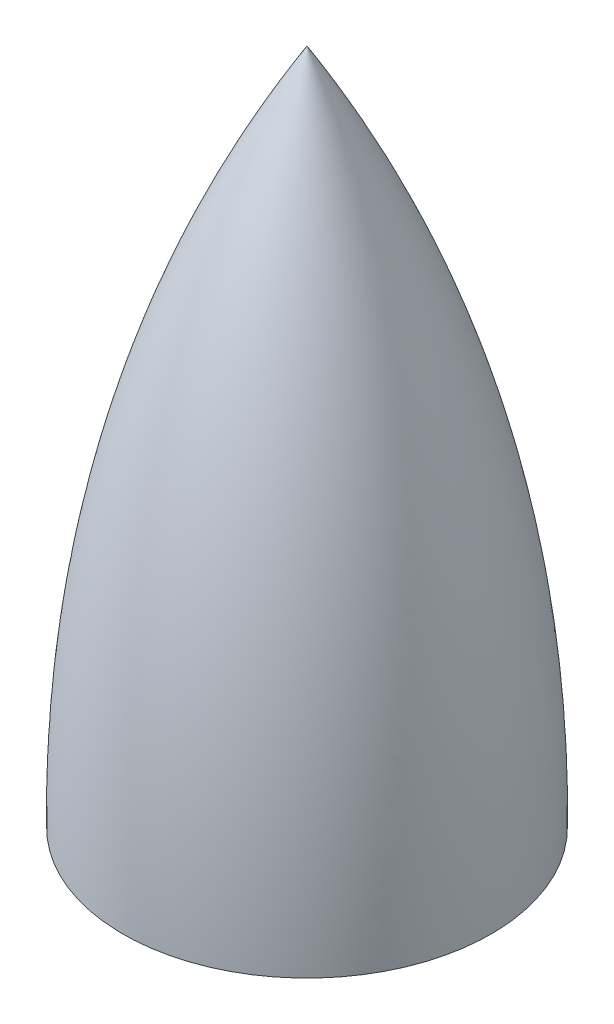
SolidWorks part; units mm, degrees
ref_plane "Front Plane" through (0, 0, 0) normal (0, 0, 1) x (1, 0, 0)
ref_plane "Top Plane" through (0, 0, 0) normal (0, 1, 0) x (1, 0, 0)
ref_plane "Right Plane" through (0, 0, 0) normal (1, 0, 0) x (0, 0, -1)
sketch "Sketch1" plane through (0, 0, 0) normal (0, 1, 0) x (1, 0, 0)
  circle A0 centre (0, 0) radius 101.6
sketch "Sketch2" plane through (0, 0, 0) normal (0, 0, 1) x (1, 0, 0)
  line L0 (0, 0) -> (0, 393.6864)
  line L1 (101.6, 0) -> (-101.6, 0) construction
  line L3 (0, 393.6864) -> (0, 377.4357)
  line L4 (-101.6, 0) -> (-107.95, 0)
  line L5 (-68.4237, 241.4942) -> (-71.5987, 241.4942)
  line L6 (0, 393.6864) -> (0, 396.8614)
  spline S0 degree 2 poles (-101.6, 0) (-107.046, 212.9876) (0, 393.6864) knots 0 0 0 1 1 1
  spline S1 degree 2 poles (-107.95, 0) (-109.9726, 215.1787) (0, 396.8614) knots 0 0 0 1 1 1
  dimension "D1" = 6.35
  dimension "D2" = 3.175
  dimension "D3" = 3.175
  dimension "D4" = 101.6
revolve "Revolve2" add sketch "Sketch2" angle 360 about L0
